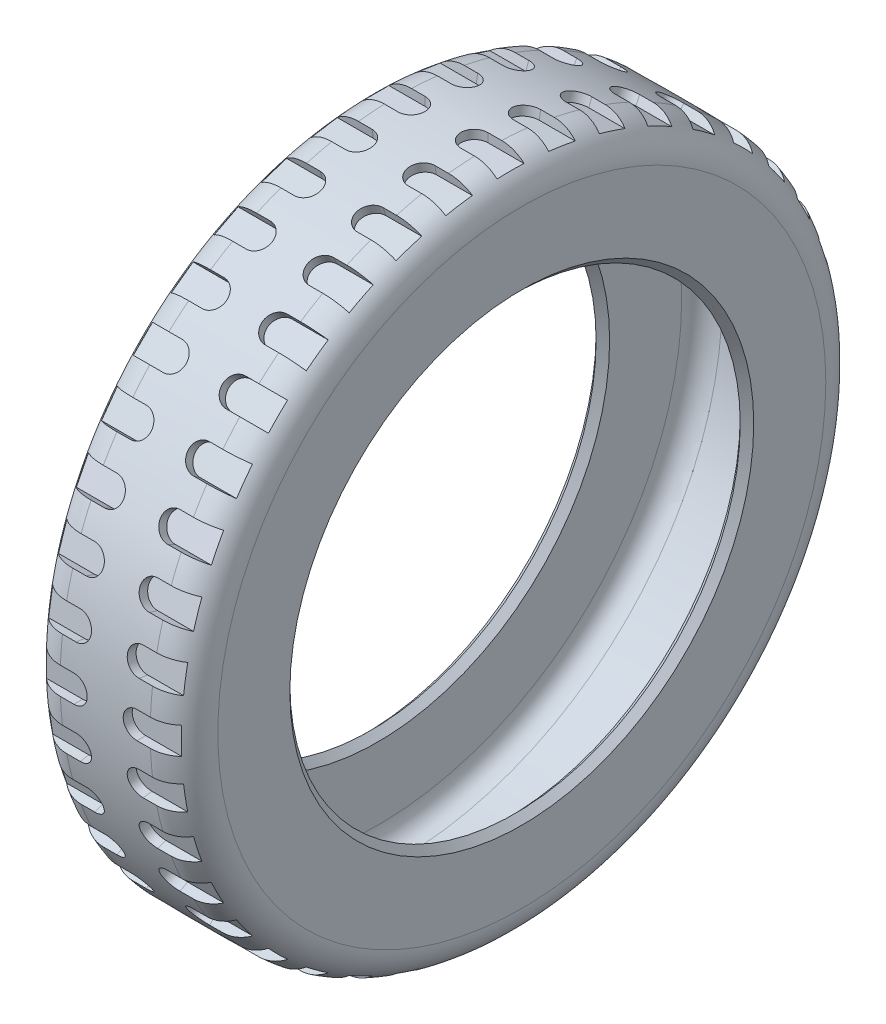
SolidWorks part; units mm, degrees
ref_plane "Front Plane" through (0, 0, 0) normal (0, 0, 1) x (1, 0, 0)
ref_plane "Top Plane" through (0, 0, 0) normal (0, 1, 0) x (1, 0, 0)
ref_plane "Right Plane" through (0, 0, 0) normal (1, 0, 0) x (0, 0, -1)
sketch "Sketch1" plane through (0, 0, 0) normal (0, 0, 1) x (1, 0, 0)
  line L0 (0, 75) -> (0, 0) construction
  line L1 (0, 0) -> (-44.9223, 0) construction
  line L2 (-14.5, 50) -> (-14.5, 67.5)
  line L3 (-17.5, 50) -> (-17.5, 67.5)
  line L4 (-10, 75) -> (10, 75)
  line L5 (17.5, 67.5) -> (17.5, 50)
  line L6 (-10, 72) -> (10, 72)
  line L7 (14.5, 67.5) -> (14.5, 50)
  line L8 (-17.5, 50) -> (-14.5, 50)
  line L9 (14.5, 50) -> (17.5, 50)
  arc A0 (10, 75) -> (17.5, 67.5) centre (10, 67.5) cw
  arc A1 (-17.5, 67.5) -> (-10, 75) centre (-10, 67.5) cw
  arc A2 (-14.5, 67.5) -> (-10, 72) centre (-10, 67.5) cw
  arc A3 (10, 72) -> (14.5, 67.5) centre (10, 67.5) cw
  point P12 (17.5, 75)
  point P15 (-17.5, 75)
  dimension "D4" = 7.5
  dimension "D1" = 35
  dimension "D2" = 75
  dimension "D3" = 50
  dimension "D5" = 3
revolve "Revolve1" add sketch "Sketch1" angle 360 about L1
chamfer "Chamfer1" distance 1.5 angle 45 4 edges at (-17.5, 0, -50) (-14.5, 0, -50) (14.5, 0, -50) (17.5, 0, -50)
ref_plane "Plane1" through (0, 0, 75) normal (0, 0, 1) x (1, 0, 0)
sketch "Sketch3" plane through (0, 0, 75) normal (0, 0, 1) x (1, 0, 0)
  line L0 (0, 0) -> (17.5, 0) construction
  line L1 (17.5, -67.5) -> (17.5, 67.5) construction
  line L3 (7, 3) -> (15, 3)
  line L5 (7, -3) -> (15, -3)
  line L6 (15, 3) -> (15, -3)
  arc A0 (7, 3) -> (7, -3) centre (7, 0) ccw
  dimension "D3" = 3
  dimension "D1" = 7
  dimension "D2" = 2.5
  dimension "D4" = 6
extrude "Cut-Extrude1" cut sketch "Sketch3" against normal blind 2
pattern_circular "CirPattern1" count 40 over 360 about axis through (16, 0, 0) along (1, 0, 0) of "Cut-Extrude1"
mirror "Mirror1" about plane through (0, 0, 0) normal (1, 0, 0) of "CirPattern1"
